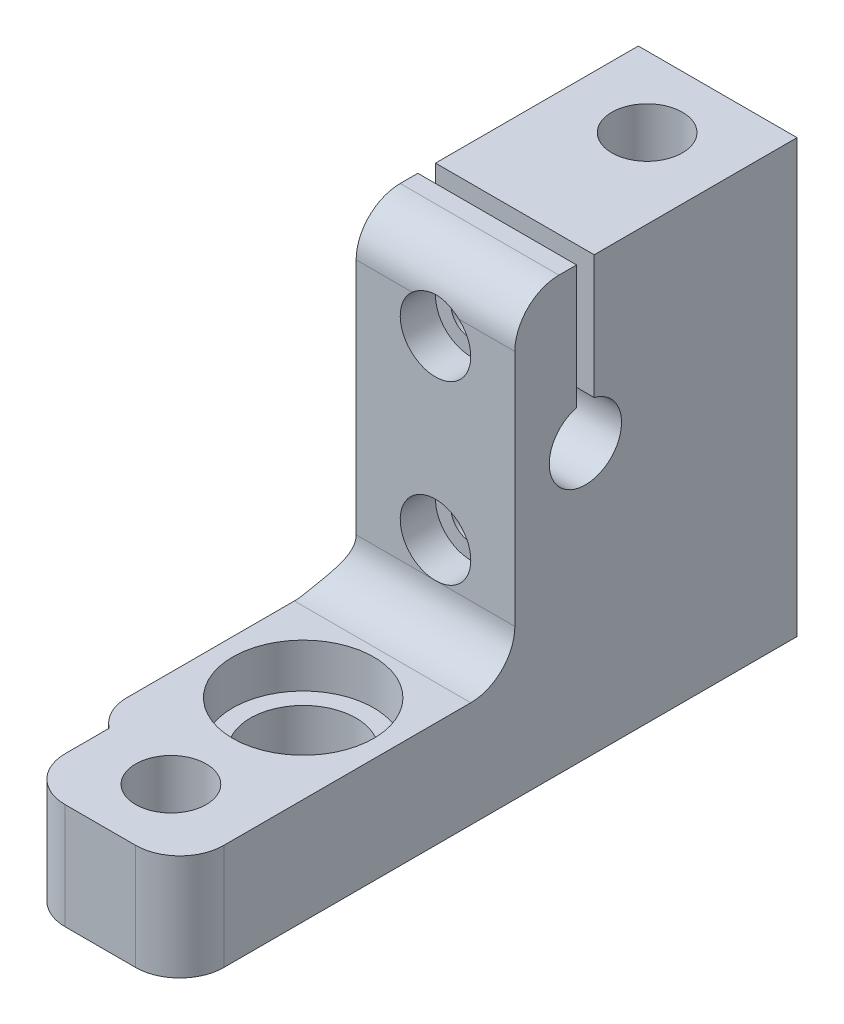
SolidWorks part; units mm, degrees
ref_plane "Спереди" through (0, 0, 0) normal (0, 0, 1) x (1, 0, 0)
ref_plane "Сверху" through (0, 0, 0) normal (0, 1, 0) x (1, 0, 0)
ref_plane "Справа" through (0, 0, 0) normal (1, 0, 0) x (0, 0, -1)
sketch "Эскиз2" plane through (0, 0, 0) normal (0, 1, 0) x (1, 0, 0)
  line L1 (-9, 16) -> (9, 16)
  line L2 (-9, 16) -> (-9, -16)
  line L3 (-9, -16) -> (9, -16)
  line L4 (9, 16) -> (9, -16)
  line L5 (-9, 16) -> (9, -16) construction
  line L6 (-9, -16) -> (9, 16) construction
  point P0 (0, 0)
  dimension "D1" = 32
  dimension "D2" = 18
extrude "Бобышка-Вытянуть1" add sketch "Эскиз2" along normal blind 49
sketch "Эскиз3" plane through (9, 0, -3.2795) normal (1, 0, 0) x (0, 0, -1)
  line L0 (12.7205, 49) -> (12.7205, 0) construction
  line L2 (-19.2795, 0) -> (12.7205, 0) construction
  circle A0 centre (-11.2795, 31) radius 4.1
  dimension "D1" = 8.2
  dimension "D2" = 31
  dimension "D3" = 24
extrude "Вырез-Вытянуть1" cut sketch "Эскиз3" against normal blind 27.3
sketch "Эскиз16" plane through (0, 0, 0) normal (0, -1, 0) x (1, 0, 0)
  line L1 (9, 16) -> (-11, 16)
  line L2 (9, 16) -> (9, 44)
  line L3 (9, 44) -> (-11, 44)
  line L4 (-11, 16) -> (-11, 44)
  dimension "D1" = 20
  dimension "D2" = 28
extrude "Бобышка-Вытянуть3" add sketch "Эскиз16" against normal blind 12
sketch "Эскиз17" plane through (0, 0, 16) normal (0, 0, 1) x (1, 0, 0)
  line L0 (-9, 49) -> (9, 49) construction
  circle A0 centre (0, 41) radius 2.25
  circle A1 centre (0, 21) radius 2.25
  point P5 (0, 49)
  dimension "D1" = 4.5
  dimension "D2" = 8
  dimension "D3" = 20
extrude "Вырез-Вытянуть3" cut sketch "Эскиз17" against normal blind 66
sketch "Эскиз18" plane through (0, 0, -16) normal (0, 0, -1) x (-1, 0, 0)
  line L1 (3, 5) -> (-3, 5)
  line L2 (3, 5) -> (3, 14)
  line L3 (3, 14) -> (-3, 14)
  line L4 (-3, 5) -> (-3, 14)
  line L5 (3, 28) -> (-3, 28)
  line L6 (3, 28) -> (3, 34)
  line L7 (3, 34) -> (-3, 34)
  line L8 (-3, 28) -> (-3, 34)
  line L9 (-9, 0) -> (9, 0) construction
  circle A1 centre (0, 21) radius 2.25 construction
  circle A2 centre (0, 41) radius 2.25 construction
  point P8 (0, 5)
  point P12 (0, 0)
  dimension "D3" = 7
  dimension "D1" = 6
  dimension "D2" = 5
  dimension "D4" = 7
  dimension "D5" = 7
extrude "Бобышка-Вытянуть4" add sketch "Эскиз18" along normal blind 4
sketch "Эскиз19" plane through (0, 0, 16) normal (0, 0, 1) x (1, 0, 0)
  circle A0 centre (0, 21) radius 4
  circle A1 centre (0, 41) radius 4
  dimension "D1" = 8
extrude "Вырез-Вытянуть4" cut sketch "Эскиз19" against normal blind 4
sketch "Эскиз20" plane through (0, 12, 0) normal (0, 1, 0) x (1, 0, 0)
  line L1 (9, 16) -> (-9, 16) construction
  line L2 (9, -16) -> (9, -44) construction
  circle A0 centre (-1, -30) radius 8
  circle A1 centre (-1, -30) radius 6
  dimension "D1" = 16
  dimension "D2" = 12
  dimension "D3" = 46
  dimension "D4" = 10
sketch "Эскиз23" plane through (0, 0, 0) normal (0, -1, 0) x (1, 0, 0)
  line L0 (-9, -16) -> (-9, 16) construction
  line L1 (9, 44) -> (-9, 44)
  line L2 (9, 44) -> (9, 54)
  line L3 (9, 54) -> (-9, 54)
  line L4 (-9, 44) -> (-9, 54)
  dimension "D1" = 10
extrude "Бобышка-Вытянуть5" add sketch "Эскиз23" against normal up to surface (12 mm away) up to face at (-2.6, 12, 27.2)
sketch "Эскиз4" plane through (0, 0, 0) normal (0, -1, 0) x (1, 0, 0)
  line L0 (9, -16) -> (-9, -16) construction
  line L2 (-9, 54) -> (9, 54) construction
  circle A0 centre (0, 46) radius 2.25
  circle A1 centre (0, -8) radius 2.25
  dimension "D3" = 4.5
  dimension "D1" = 8
  dimension "D2" = 8
extrude "Вырез-Вытянуть2" cut sketch "Эскиз4" against normal through all
sketch "Эскиз8" plane through (0, 0, 0) normal (0, -1, 0) x (1, 0, 0)
  line L0 (9, -16) -> (-9, -16) construction
  line L1 (-3, 0) -> (3, 0)
  line L2 (-3, 0) -> (-3, 38)
  line L3 (-3, 38) -> (3, 38)
  line L4 (3, 0) -> (3, 38)
  line L6 (3, 34.8874) -> (-3, 34.8874)
  line L7 (3, 34.8874) -> (3, 24.7217)
  line L8 (3, 24.7217) -> (-3, 24.7217)
  line L9 (-3, 34.8874) -> (-3, 24.7217)
  circle A0 centre (0, -8) radius 2.25 construction
  circle A1 centre (0, 46) radius 2.25 construction
  point P0 (0, -11.3393)
  point P6 (0, 0)
  point P9 (0, -16)
  dimension "D2" = 8
  dimension "D3" = 8
  dimension "D1" = 6
extrude "Вырез-Вытянуть5" cut sketch "Эскиз20" against normal blind 5
extrude "Бобышка-Вытянуть7" add sketch "Эскиз8" along normal blind 4 contours L6 L4 L3 L2 | L4 L8 L2 L1 region at (0, 0, 12.3608) region at (0, 0, 36.4437)
extrude "Вырез-Вытянуть7" cut sketch "Эскиз20<4>" against normal blind 25 contours A1 region at (-1, 12, 30)
sketch "Эскиз20<4>" plane through (0, 12, 0) normal (0, 1, 0) x (1, 0, 0) same geometry as "Эскиз20"
fillet "Скругление1" radius 5 2 edges at (-11, 6, 44) (-11, 6, 16)
fillet "Скругление2" radius 5 4 edges at (0, 12, 16) (0, 49, 16) (9, 6, 54) (-9, 6, 54)
sketch "Эскиз24" plane through (9, 0, 0) normal (1, 0, 0) x (0, 0, -1)
  line L0 (-11, 49) -> (16, 49) construction
  line L1 (-7, 49) -> (-9, 49)
  line L2 (-7, 49) -> (-7, 31)
  line L3 (-7, 31) -> (-9, 31)
  line L4 (-9, 49) -> (-9, 31)
  circle A0 centre (-8, 31) radius 4.1 construction
  point P6 (-8, 31)
  dimension "D1" = 2
extrude "Вырез-Вытянуть8" cut sketch "Эскиз24" against normal blind 23
sketch "Эскиз25" plane through (0, 49, 0) normal (0, 1, 0) x (1, 0, 0)
  circle A0 centre (0, 8) radius 4
  circle A1 centre (0, -46) radius 4
  circle A2 centre (0, -46) radius 2.25 construction
  dimension "D1" = 8
extrude "Вырез-Вытянуть9" cut sketch "Эскиз25" against normal blind 45
